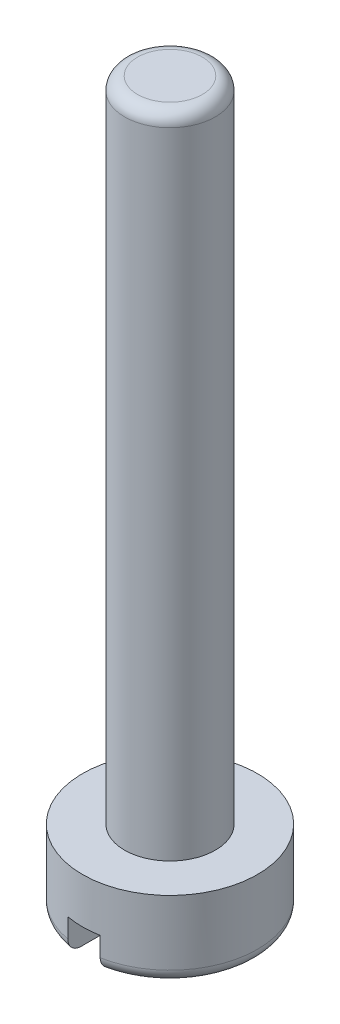
SolidWorks part; units mm, degrees
ref_plane "Front Plane" through (0, 0, 0) normal (0, 0, 1) x (1, 0, 0)
ref_plane "Top Plane" through (0, 0, 0) normal (0, 1, 0) x (1, 0, 0)
ref_plane "Right Plane" through (0, 0, 0) normal (1, 0, 0) x (0, 0, -1)
sketch "Sketch2" plane through (0, 0, 0) normal (0, 1, 0) x (1, 0, 0)
  circle A0 centre (0, 0) radius 1.35
  dimension "D1" = 2.7
extrude "Boss-Extrude1" add sketch "Sketch2" along normal blind 1.2
sketch "Sketch3" plane through (0, 1.2, 0) normal (0, 1, 0) x (1, 0, 0)
  circle A0 centre (0, 0) radius 0.7
  dimension "D1" = 1.4
extrude "Boss-Extrude2" add sketch "Sketch3" along normal blind 10
sketch "Sketch4" plane through (0, 0, 0) normal (0, 0, 1) x (1, 0, 0)
  line L0 (-0.25, 0) -> (0.25, 0)
  line L1 (-1.35, 0) -> (1.35, 0) construction
  line L2 (-0.25, 0) -> (-0.25, 0.5)
  line L3 (-0.25, 0.5) -> (0.25, 0.5)
  line L4 (0.25, 0.5) -> (0.25, 0)
  point P6 (0, 0)
  dimension "D1" = 0.5
  dimension "D2" = 0.5
extrude "Cut-Extrude1" cut sketch "Sketch4" against normal blind 10 and the other way blind 10
fillet "Fillet1" radius 0.2 3 edges at (1.35, 0, 0) (-1.35, 0, 0) (0, 11.2, 0.7)
